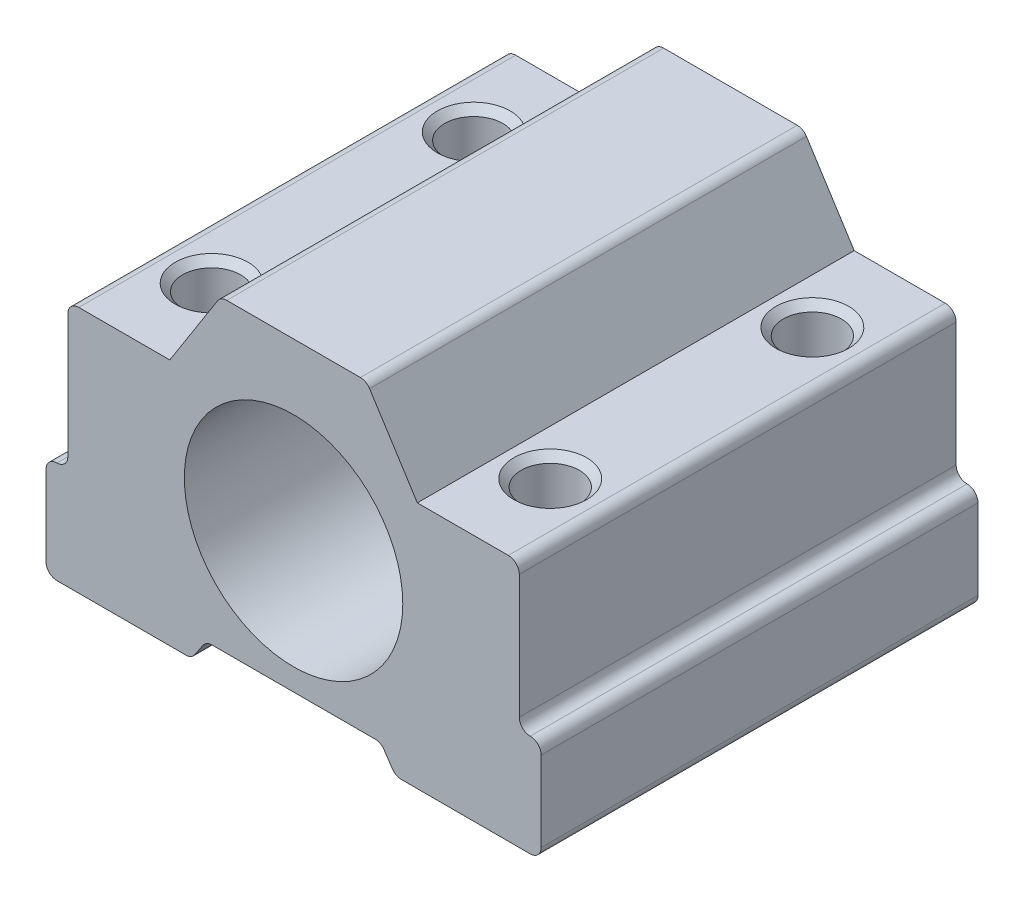
SolidWorks part; units mm, degrees
ref_plane "前视基准面" through (0, 0, 0) normal (0, 0, 1) x (1, 0, 0)
ref_plane "上视基准面" through (0, 0, 0) normal (0, 1, 0) x (1, 0, 0)
ref_plane "右视基准面" through (0, 0, 0) normal (1, 0, 0) x (0, 0, -1)
sketch "草图1" plane through (0, 0, 0) normal (0, 0, 1) x (1, 0, 0)
  line L0 (5, 11.25) -> (-5, 11.25)
  line L2 (-17, -4.25) -> (-17, -11.25)
  line L3 (-17, -11.25) -> (-7, -11.25)
  line L5 (-17, 11.25) -> (17, -11.25) construction
  line L6 (-17, -11.25) -> (17, 11.25) construction
  line L7 (0, 11.25) -> (0, -11.25) construction
  line L8 (-8.5, 5.75) -> (-15.5, 5.75)
  line L9 (6, -9.75) -> (-6, -9.75)
  line L10 (-8.5, 5.75) -> (-5, 11.25)
  line L11 (-15.5, -4.25) -> (-17, -4.25)
  line L12 (-15.5, -4.25) -> (-15.5, 5.75)
  line L13 (6, -9.75) -> (7, -11.25)
  line L14 (-6, -9.75) -> (-7, -11.25)
  line L15 (17, -11.25) -> (7, -11.25)
  line L16 (17, -4.25) -> (17, -11.25)
  line L17 (15.5, -4.25) -> (17, -4.25)
  line L18 (15.5, -4.25) -> (15.5, 5.75)
  line L19 (8.5, 5.75) -> (15.5, 5.75)
  line L20 (8.5, 5.75) -> (5, 11.25)
  circle A0 centre (0, -0.75) radius 7.5
  point P0 (0, 0)
  point P17 (0, -9.75)
  dimension "D1" = 12
  dimension "D2" = 5
  dimension "D3" = 17
  dimension "D4" = 22.5
  dimension "D5" = 8.5
  dimension "D6" = 10
  dimension "D7" = 10
  dimension "D9" = 6
extrude "凸台-拉伸1" add sketch "草图1" along normal blind 30
fillet "圆角1" radius 0.75 14 edges at (-17, -11.25, 15) (-7, -11.25, 15) (-6, -9.75, 15) (7, -11.25, 15) (6, -9.75, 15) (17, -11.25, 15) (17, -4.25, 15) (15.5, -4.25, 15) (15.5, 5.75, 15) (5, 11.25, 15) (-5, 11.25, 15) (-17, -4.25, 15) (-15.5, -4.25, 15) (-15.5, 5.75, 15)
sketch "草图2" plane through (0, 5.75, 0) normal (0, 1, 0) x (1, 0, 0)
  line L0 (0, 0) -> (0, -30) construction
  line L1 (-8.5, 0) -> (-14.75, 0) construction
  line L2 (4.5883, -30) -> (-4.5883, -30) construction
  circle A0 centre (-11.625, -6) radius 2
  circle A1 centre (-11.625, -24) radius 2
  circle A2 centre (11.625, -24) radius 2
  circle A3 centre (11.625, -6) radius 2
  dimension "D1" = 4
  dimension "D2" = 4
  dimension "D3" = 18
  dimension "D4" = 6
extrude "切除-拉伸1" cut sketch "草图2" against normal through all
chamfer "倒角1" distance 0.5 angle 45 8 edges at (13.625, 5.75, 24) (-13.625, 5.75, 24) (-13.625, 5.75, 6) (13.625, 5.75, 6) (-13.625, -11.25, 6) (-13.625, -11.25, 24) (13.625, -11.25, 24) (13.625, -11.25, 6)
